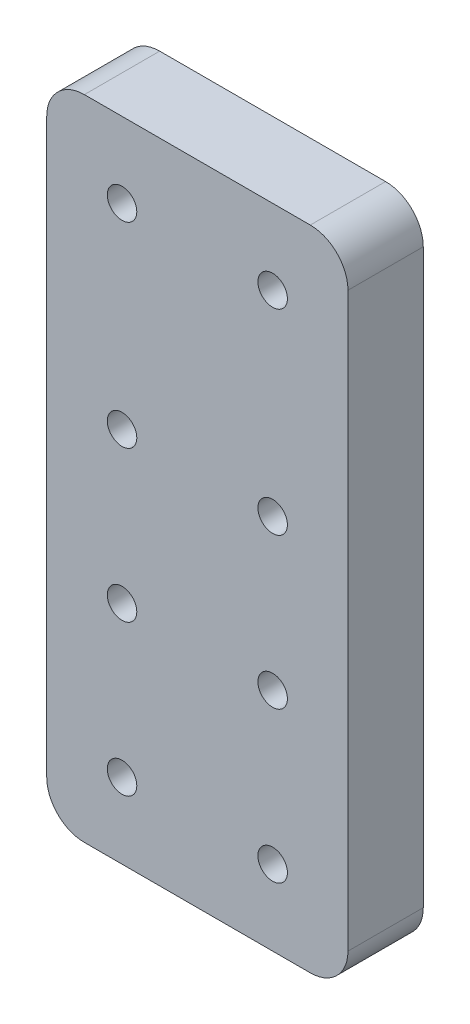
SolidWorks part; units mm, degrees
material "PET"
ref_plane "Front Plane" through (0, 0, 0) normal (0, 0, 1) x (1, 0, 0)
ref_plane "Top Plane" through (0, 0, 0) normal (0, 1, 0) x (1, 0, 0)
ref_plane "Right Plane" through (0, 0, 0) normal (1, 0, 0) x (0, 0, -1)
sketch "Sketch2" plane through (0, 0, 0) normal (0, 0, 1) x (1, 0, 0)
  line L1 (0, 0) -> (50.8, 0)
  line L2 (0, 0) -> (0, 109.22)
  line L3 (0, 109.22) -> (50.8, 109.22)
  line L4 (50.8, 0) -> (50.8, 109.22)
  dimension "D1" = 50.8
  dimension "D2" = 109.22
extrude "Boss-Extrude1" add sketch "Sketch2" against normal blind 12.7
sketch "Sketch3" plane through (0, 0, 0) normal (0, 0, 1) x (1, 0, 0)
  line L0 (50.8, 109.22) -> (0, 109.22) construction
  line L1 (0, 109.22) -> (0, 0) construction
  circle A0 centre (12.7, 96.52) radius 2.4892
  circle A17 centre (38.1, 96.52) radius 2.4892
  circle A24 centre (12.7, 63.5) radius 2.4892
  circle A25 centre (12.7, 38.1) radius 2.4892
  circle A26 centre (12.7, 12.7) radius 2.4892
  circle A27 centre (12.7, -12.7) radius 2.4892
  circle A28 centre (12.7, -38.1) radius 2.4892
  circle A33 centre (38.1, 38.1) radius 2.4892
  circle A34 centre (38.1, 12.7) radius 2.4892
  circle A35 centre (38.1, -12.7) radius 2.4892
  circle A36 centre (38.1, -38.1) radius 2.4892
  circle A41 centre (38.1, 63.5) radius 2.4892
  dimension "D1" = 4.9784
  dimension "D6" = 4.9784
  dimension "D2" = 12.7
  dimension "D3" = 12.7
  dimension "D7" = 12.7
  dimension "D8" = 33.02
  dimension "D4" = 1
  dimension "D5" = 2
  dimension "D9" = 5
  dimension "D10" = 2
extrude "Cut-Extrude1" cut sketch "Sketch3" against normal through all
fillet "Fillet1" radius 6.35 4 edges at (0, 0, -6.35) (50.8, 0, -6.35) (50.8, 109.22, -6.35) (0, 109.22, -6.35)
